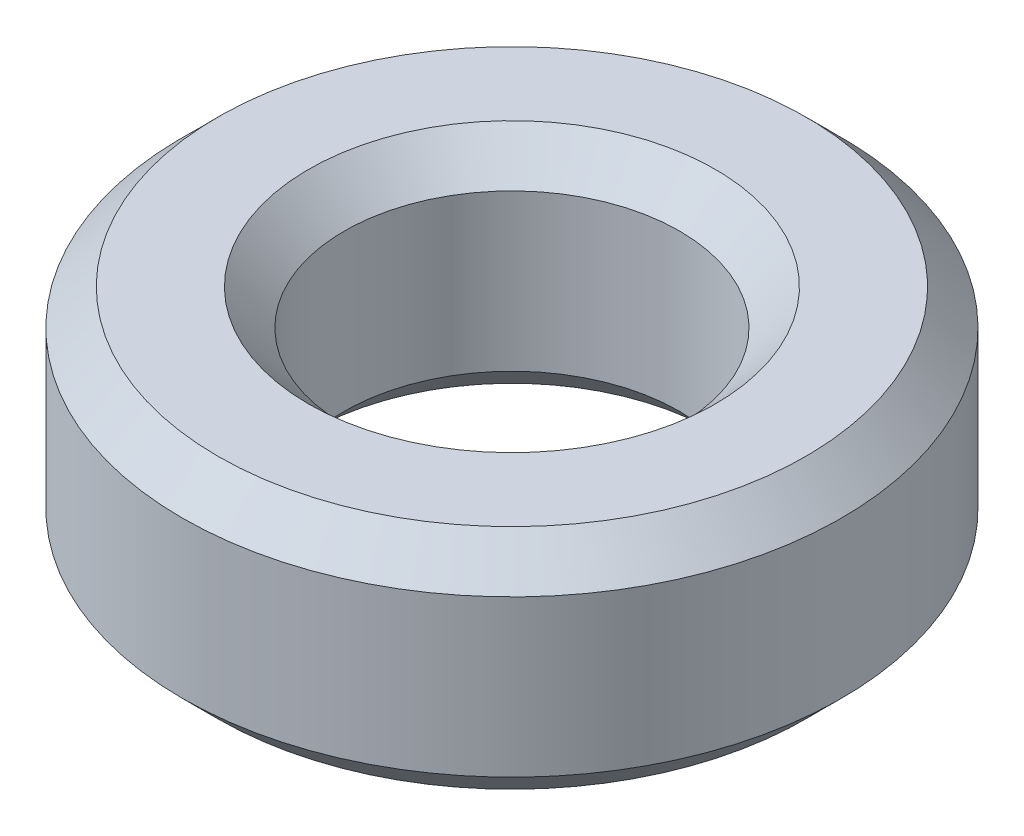
SolidWorks part; units mm, degrees
ref_plane "Front Plane" through (0, 0, 0) normal (0, 0, 1) x (1, 0, 0)
ref_plane "Top Plane" through (0, 0, 0) normal (0, 1, 0) x (1, 0, 0)
ref_plane "Right Plane" through (0, 0, 0) normal (1, 0, 0) x (0, 0, -1)
sketch "Sketch1" plane through (0, 0, 0) normal (0, 1, 0) x (1, 0, 0)
  circle A0 centre (0, 0) radius 20
  dimension "SLEEVE_OD" = 40
extrude "Boss-Extrude1" add sketch "Sketch1" along normal blind 13.8017
sketch "Sketch2" plane through (0, 0, 0) normal (0, 1, 0) x (1, 0, 0)
  circle A0 centre (0, 0) radius 10.1751
  dimension "BORE_D" = 20.3503
extrude "Cut-Extrude1" cut sketch "Sketch2" along normal through all
chamfer "Chamfer1" distance 2.163 angle 45 4 edges at (0, 13.8017, 10.1751) (0, 0, 10.1751) (0, 0, 20) (0, 13.8017, 20)
